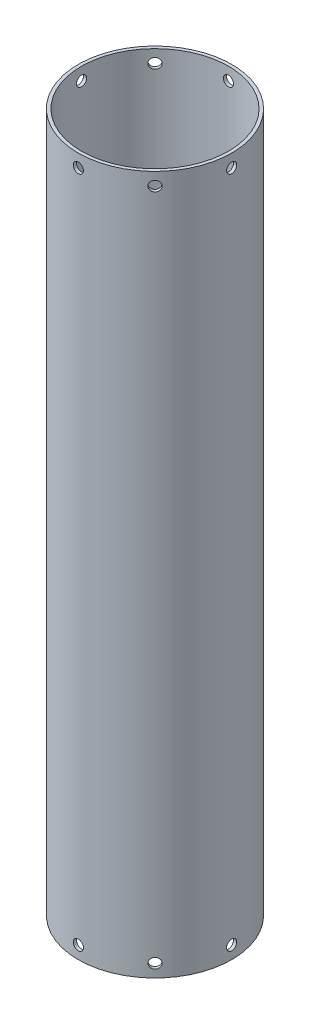
SolidWorks part; units mm, degrees
material "6061-T6 (SS)"
ref_plane "Front Plane" through (0, 0, 0) normal (0, 0, 1) x (1, 0, 0)
ref_plane "Top Plane" through (0, 0, 0) normal (0, 1, 0) x (1, 0, 0)
ref_plane "Right Plane" through (0, 0, 0) normal (1, 0, 0) x (0, 0, -1)
sketch "Sketch1" plane through (0, 0, 0) normal (0, 1, 0) x (1, 0, 0)
  circle A0 centre (0, 0) radius 76.2
  circle A1 centre (0, 0) radius 73.025
  dimension "D1" = 152.4
  dimension "D2" = 3.175
extrude "Boss-Extrude1" add sketch "Sketch1" along normal blind 693.1406
sketch "Sketch2" plane through (0, 667.7406, 0) normal (1, 0, 0) x (0, 0, 1)
  circle A0 centre (0, -12.7) radius 4.7625 construction
  circle A1 centre (0, -12.7) radius 4.7625 construction
  circle A2 centre (0, -12.7) radius 5.0165
  dimension "D1" = 0.254
extrude "LOX Top Holes" cut sketch "Sketch2" along normal up to surface (76.0347 mm away) contours A2 region at (0, 680.4406, 0) up to face at (0, 693.1406, 76.2)
pattern_circular "CirPattern1" count 8 over 360 about axis through (0, 693.1406, 0) along (0, 1, 0) of "LOX Top Holes"
sketch "Sketch3" plane through (0, 25.4, 0) normal (1, 0, 0) x (0, 0, -1)
  circle A0 centre (0, -12.7) radius 4.7625 construction
  circle A1 centre (0, -12.7) radius 4.7625 construction
  circle A2 centre (0, -12.7) radius 5.0165
  dimension "D1" = 0.254
extrude "LOX Bottom Holes" cut sketch "Sketch3" along normal up to surface (76.0347 mm away) contours A2 region at (0, 12.7, 0) up to face at (0, 693.1406, 76.2)
pattern_circular "CirPattern2" count 8 over 360 about axis through (0, 0, 0) along (0, 1, 0) of "LOX Bottom Holes"
sketch "Sketch4" [suppressed] plane through (0, 442.595, 0) normal (1, 0, 0) x (0, 0, 1)
  circle A0 centre (0, -12.7) radius 4.7625 construction
  circle A1 centre (0, -12.7) radius 4.7625 construction
  circle A2 centre (0, -12.7) radius 5.0165
  dimension "D1" = 0.254
extrude "Cut-Extrude1" [suppressed] cut sketch "Sketch4" along normal up to surface (76.0347 mm away) contours A2 up to face at (0, 693.1406, 76.2)
pattern_circular "CirPattern3" [suppressed] count 8 over 360 of bodies 126
sketch "Sketch7" [suppressed] plane through (0, 25.4, 0) normal (1, 0, 0) x (0, 0, -1)
  circle A0 centre (0, -12.7) radius 4.7625 construction
  circle A1 centre (0, -12.7) radius 4.7625 construction
  circle A2 centre (0, -12.7) radius 5.0165
  dimension "D1" = 0.254
extrude "Cut-Extrude2" [suppressed] cut sketch "Sketch7" along normal up to surface (76.0347 mm away) up to face at (0, 693.1406, 76.2)
pattern_circular "CirPattern4" [suppressed] count 8 over 360 of bodies 128
